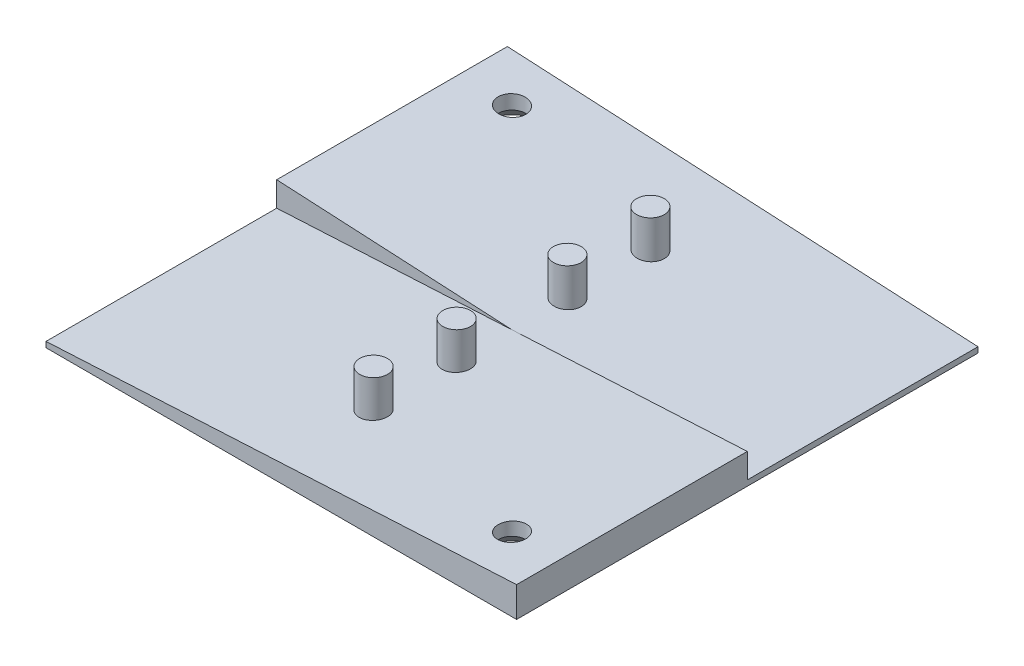
SolidWorks part; units mm, degrees
material "ABS"
ref_plane "Plano frontal" through (0, 0, 0) normal (0, 0, 1) x (1, 0, 0)
ref_plane "Plano superior" through (0, 0, 0) normal (0, 1, 0) x (1, 0, 0)
ref_plane "Plano direito" through (0, 0, 0) normal (1, 0, 0) x (0, 0, -1)
sketch "Esboço2" plane through (0, 0, 0) normal (0, 1, 0) x (1, 0, 0)
  line L7 (25.5, 25) -> (-25.5, 25)
  line L8 (25.5, 25) -> (25.5, -25)
  line L9 (25.5, -25) -> (-25.5, -25)
  line L10 (-25.5, 25) -> (-25.5, -25)
  line L11 (25.5, 25) -> (-25.5, -25) construction
  line L12 (25.5, -25) -> (-25.5, 25) construction
  point P0 (0, 0)
  dimension "D1" = 50
  dimension "D2" = 51
extrude "Ressalto-extrusão2" add sketch "Esboço2" along normal blind 6
sketch "Esboço3" plane through (0, 0, 25) normal (0, 0, 1) x (1, 0, 0)
  line L0 (-25.5, 0.6) -> (25.5, 3.2728)
  line L1 (25.5, 6) -> (25.5, 0) construction
  line L2 (-25.5, 6) -> (-25.5, 0) construction
  line L3 (-25.5, 0) -> (25.5, 0) construction
  line L4 (-25.5, 0.6) -> (-25.5, 6)
  line L5 (-25.5, 6) -> (25.5, 6)
  line L6 (25.5, 6) -> (25.5, 3.2728)
  dimension "D1" = 3
  dimension "D2" = 0.6
extrude "Corte-extrusão1" cut sketch "Esboço3" against normal blind 25
sketch "Esboço4" plane through (0, 0, -25) normal (0, 0, -1) x (-1, 0, 0)
  line L0 (-25.5, 0.6) -> (25.5, 3.2728)
  line L1 (-25.5, 6) -> (-25.5, 0) construction
  line L2 (25.5, 6) -> (25.5, 0) construction
  line L3 (-25.5, 0.6) -> (-25.5, 6)
  line L4 (-25.5, 6) -> (25.5, 6)
  line L5 (25.5, 6) -> (25.5, 3.2728)
  line L7 (-25.5, 0) -> (25.5, 0) construction
  dimension "D1" = 0.6
  dimension "D2" = 3
extrude "Corte-extrusão3" cut sketch "Esboço4" against normal blind 25
sketch "Esboço5" plane through (0, 0, 0) normal (0, -1, 0) x (1, 0, 0)
  line L0 (0, 6) -> (0, -6) construction
  circle A0 centre (0, 6) radius 1.5
  circle A1 centre (0, 15) radius 1.5
  circle A2 centre (0, -15) radius 1.5
  circle A3 centre (0, -6) radius 1.5
  point P12 (0, 0)
  dimension "D1" = 3
  dimension "D2" = 3
  dimension "D3" = 15
  dimension "D4" = 6
  dimension "D5" = 15
extrude "Ressalto-extrusão3" add sketch "Esboço5" against normal blind 6
sketch "Esboço8" plane through (0, 0, 0) normal (0, -1, 0) x (1, 0, 0)
  line L1 (20, 20) -> (-20, 20) construction
  line L2 (20, 20) -> (20, -20) construction
  line L3 (20, -20) -> (-20, -20) construction
  line L4 (-20, 20) -> (-20, -20) construction
  line L5 (20, 20) -> (-20, -20) construction
  line L6 (20, -20) -> (-20, 20) construction
  circle A1 centre (20, 20) radius 1.5
  circle A3 centre (-20, -20) radius 1.5
  point P8 (0, 0)
  dimension "D1" = 3
  dimension "D3" = 3
  dimension "D2" = 40
extrude "Corte-extrusão6" cut sketch "Esboço8" against normal through all
chamfer "Chanfro1" distance 1.5 angle 45 2 edges at (-20, 0, -21.5) (20, 0, 18.5)
equation "\"D5@Esboço5\"=\"D3@Esboço5\""
